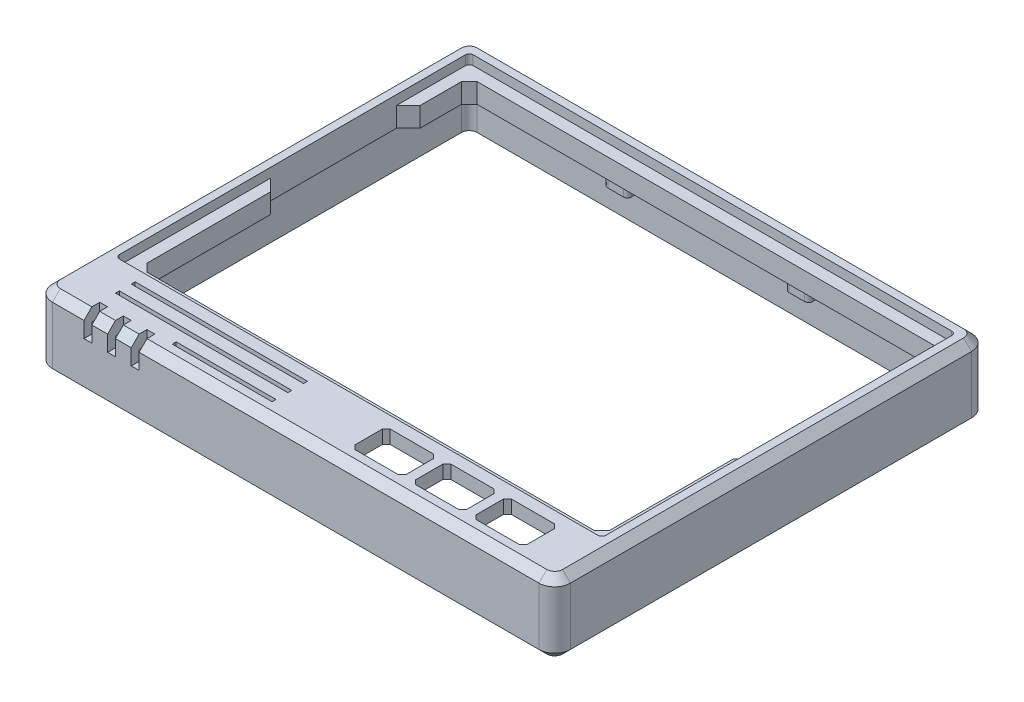
SolidWorks part; units mm, degrees
ref_plane "前视基准面" through (0, 0, 0) normal (0, 0, 1) x (1, 0, 0)
ref_plane "上视基准面" through (0, 0, 0) normal (0, 1, 0) x (1, 0, 0)
ref_plane "右视基准面" through (0, 0, 0) normal (1, 0, 0) x (0, 0, -1)
other "Configuration Table"
sketch "草图1" plane through (0, 0, 0) normal (0, 1, 0) x (1, 0, 0)
  line L1 (-33.1238, 22.1068) -> (32.6362, 22.1068)
  line L2 (-33.1238, 22.1068) -> (-33.1238, -32.8132)
  line L3 (-33.1238, -32.8132) -> (32.6362, -32.8132)
  line L4 (32.6362, 22.1068) -> (32.6362, -32.8132)
  dimension "D1" = 65.76
  dimension "D2" = 54.92
extrude "凸台-拉伸1" add sketch "草图1" against normal blind 9.3
sketch "草图2" plane through (0, 0, 0) normal (0, 1, 0) x (1, 0, 0)
  line L1 (-30.6238, 20.1068) -> (30.1262, 20.1068)
  line L2 (-31.1238, 19.6068) -> (-31.1238, -24.3132)
  line L3 (-30.6238, -24.8132) -> (30.1262, -24.8132)
  line L4 (30.6262, 19.6068) -> (30.6262, -24.3132)
  line L6 (-33.1238, 22.1068) -> (-33.1238, -32.8132) construction
  line L8 (32.6362, 22.1068) -> (-33.1238, 22.1068) construction
  arc A0 (-31.1238, -24.3132) -> (-30.6238, -24.8132) centre (-30.6238, -24.3132) ccw
  arc A1 (30.1262, -24.8132) -> (30.6262, -24.3132) centre (30.1262, -24.3132) ccw
  arc A2 (30.1262, 20.1068) -> (30.6262, 19.6068) centre (30.1262, 19.6068) cw
  arc A3 (-30.6238, 20.1068) -> (-31.1238, 19.6068) centre (-30.6238, 19.6068) ccw
  point P12 (30.6262, -24.8132)
  point P15 (30.6262, 20.1068)
  point P18 (-31.1238, 20.1068)
  dimension "D5" = 0.5
  dimension "D1" = 61.75
  dimension "D2" = 44.92
  dimension "D3" = 2
  dimension "D4" = 2
fillet "圆角1" radius 2 2 edges at (32.6362, -4.65, -22.1068) (-33.1238, -4.65, -22.1068)
extrude "切除-拉伸1" cut sketch "草图2" against normal blind 1.2
sketch "草图3" plane through (0, -1.2, 0) normal (0, 1, 0) x (1, 0, 0)
  line L0 (30.1262, 20.1068) -> (-30.6238, 20.1068) construction
  line L1 (-29.6238, 18.6068) -> (29.1262, 18.6068)
  line L2 (-29.6238, 18.6068) -> (-29.6238, -23.3132)
  line L3 (-29.6238, -23.3132) -> (29.1262, -23.3132)
  line L4 (29.1262, 18.6068) -> (29.1262, -23.3132)
  line L5 (-31.1238, 19.6068) -> (-31.1238, -24.3132) construction
  line L6 (30.6262, -24.3132) -> (30.6262, 19.6068) construction
  line L7 (-30.6238, -24.8132) -> (30.1262, -24.8132) construction
  dimension "D1" = 1.5
  dimension "D2" = 1.5
  dimension "D3" = 1.5
  dimension "D4" = 1.5
extrude "切除-拉伸2" cut sketch "草图3" against normal blind 1
chamfer "倒角2" distance 1 angle 45 5 edges at (32.6362, 0, 6.3532) (32.0504, 0, -21.521) (-0.2438, 0, -22.1068) (-32.5381, 0, -21.521) (-33.1238, 0, 6.3532)
sketch "草图7" plane through (0, -2.2, 0) normal (0, 1, 0) x (1, 0, 0)
  line L0 (-29.6238, -23.3132) -> (29.1262, -23.3132) construction
  line L1 (-29.6238, 18.6068) -> (-27.6238, 18.6068)
  line L2 (-29.6238, 18.6068) -> (-29.6238, -23.3132)
  line L3 (-29.6238, -23.3132) -> (-27.6238, -23.3132)
  line L4 (-27.6238, 18.6068) -> (-27.6238, -23.3132)
  dimension "D1" = 2
extrude "切除-拉伸5" cut sketch "草图7" against normal through all
sketch "草图8" plane through (0, -9.3, 0) normal (0, -1, 0) x (1, 0, 0)
  line L74 (-31.1238, -21.1068) -> (30.6362, -21.1068)
  line L75 (31.6362, -20.1068) -> (31.6362, 31.8132)
  line L76 (31.6362, 31.8132) -> (-32.1238, 31.8132)
  line L77 (-32.1238, 31.8132) -> (-32.1238, -20.1068)
  line L78 (-31.1238, -21.1068) -> (30.6362, -21.1068)
  line L79 (31.6362, -20.1068) -> (31.6362, 31.8132)
  line L80 (31.6362, 31.8132) -> (-32.1238, 31.8132)
  line L81 (-32.1238, 31.8132) -> (-32.1238, -20.1068)
  arc A50 (30.6362, -21.1068) -> (31.6362, -20.1068) centre (30.6362, -20.1068) ccw
  arc A51 (30.6362, -21.1068) -> (31.6362, -20.1068) centre (30.6362, -20.1068) ccw
  arc A52 (-32.1238, -20.1068) -> (-31.1238, -21.1068) centre (-31.1238, -20.1068) ccw
  arc A53 (-32.1238, -20.1068) -> (-31.1238, -21.1068) centre (-31.1238, -20.1068) ccw
  dimension "D1" = 1
extrude "切除-拉伸6" cut sketch "草图8" against normal blind 5.8
sketch "草图10" plane through (0, -1.2, 0) normal (0, 1, 0) x (1, 0, 0)
  line L0 (30.6262, -24.3132) -> (30.6262, 19.6068) construction
  line L1 (29.1262, 18.6068) -> (30.6262, 18.6068)
  line L2 (29.1262, 18.6068) -> (29.1262, -3.6232)
  line L3 (29.1262, -3.6232) -> (30.6262, -3.6232)
  line L4 (30.6262, 18.6068) -> (30.6262, -3.6232)
  dimension "D1" = 22.23
extrude "切除-拉伸7" cut sketch "草图10" against normal blind 1
chamfer "倒角8" distance 3 angle 45 1 edges at (29.1262, -1.7, 3.6232)
chamfer "倒角9" distance 1 angle 45 3 edges at (29.1262, -1.7, 23.3132) (-29.6238, -2.35, 23.3132) (-29.6238, -2.35, -18.6068)
fillet "圆角2" radius 2 2 edges at (32.6362, -5.15, 32.8132) (-33.1238, -5.15, 32.8132)
chamfer "倒角11" distance 1 angle 45 3 edges at (-31.6415, 0, 32.7451) (31.1538, 0, 32.7451) (-0.2438, 0, 32.8132)
fillet "圆角3" radius 1 2 edges at (31.6362, -6.4, 31.8132) (-32.1238, -6.4, 31.8132)
sketch "草图14" plane through (0, 0, 0) normal (0, 1, 0) x (1, 0, 0)
  line L0 (30.6362, -32.8132) -> (-31.1238, -32.8132) construction
  line L1 (-27.1238, -32.8132) -> (-26.1238, -32.8132)
  line L2 (-27.1238, -32.8132) -> (-27.1238, -30.8132)
  line L3 (-27.1238, -30.8132) -> (-26.1238, -30.8132)
  line L4 (-26.1238, -32.8132) -> (-26.1238, -30.8132)
  line L5 (-24.1238, -32.8132) -> (-23.1238, -32.8132)
  line L6 (-24.1238, -32.8132) -> (-24.1238, -30.8132)
  line L7 (-24.1238, -30.8132) -> (-23.1238, -30.8132)
  line L8 (-23.1238, -32.8132) -> (-23.1238, -30.8132)
  line L9 (-32.1238, 20.1068) -> (-32.1238, -30.8132) construction
  line L10 (-21.1238, -32.8132) -> (-20.1238, -32.8132)
  line L11 (-21.1238, -32.8132) -> (-21.1238, -30.8132)
  line L12 (-21.1238, -30.8132) -> (-20.1238, -30.8132)
  line L13 (-20.1238, -32.8132) -> (-20.1238, -30.8132)
  line L14 (-30.6238, -24.8132) -> (30.1262, -24.8132) construction
  line L15 (31.6362, -30.8132) -> (31.6362, 20.1068) construction
  line L16 (-17.9253, -30.3132) -> (-5.2438, -30.3132)
  line L17 (-27.1238, -26.3132) -> (-5.2438, -26.3132)
  line L22 (-27.1238, -26.3132) -> (-27.1238, -26.8132)
  line L23 (-27.1238, -26.8132) -> (-5.2438, -26.8132)
  line L24 (-5.2438, -26.3132) -> (-5.2438, -26.8132)
  line L25 (-27.1238, -28.3132) -> (-5.2438, -28.3132)
  line L26 (-27.1238, -28.3132) -> (-27.1238, -28.8132)
  line L27 (-27.1238, -28.8132) -> (-5.2438, -28.8132)
  line L28 (-5.2438, -28.3132) -> (-5.2438, -28.8132)
  line L29 (-17.9253, -30.3132) -> (-17.9253, -30.8132)
  line L30 (-17.9253, -30.8132) -> (-5.2438, -30.8132)
  line L31 (-5.2438, -30.3132) -> (-5.2438, -30.8132)
  line L32 (4.7562, -26.3132) -> (11.2562, -26.3132)
  line L33 (4.7562, -26.3132) -> (4.7562, -30.8132)
  line L34 (4.7562, -30.8132) -> (11.2562, -30.8132)
  line L35 (11.2562, -26.3132) -> (11.2562, -30.8132)
  line L36 (12.4462, -26.3132) -> (18.9462, -26.3132)
  line L37 (12.4462, -26.3132) -> (12.4462, -30.8132)
  line L38 (12.4462, -30.8132) -> (18.9462, -30.8132)
  line L39 (18.9462, -26.3132) -> (18.9462, -30.8132)
  line L40 (20.1362, -26.3132) -> (26.6362, -26.3132)
  line L41 (20.1362, -26.3132) -> (20.1362, -30.8132)
  line L42 (20.1362, -30.8132) -> (26.6362, -30.8132)
  line L43 (26.6362, -26.3132) -> (26.6362, -30.8132)
  dimension "D1" = 1
  dimension "D2" = 2
  dimension "D3" = 5
  dimension "D4" = 2
  dimension "D5" = 2
  dimension "D6" = 0.5
  dimension "D7" = 1.5
  dimension "D8" = 1.5
  dimension "D9" = 21.88
  dimension "D10" = 1.5
  dimension "D11" = 10
  dimension "D12" = 5
  dimension "D13" = 6.5
  dimension "D14" = 1.19
extrude "切除-拉伸9" cut sketch "草图14" against normal through all contours L17 L24 L23 L22 | L25 L28 L27 L26 | L16 L31 L30 L29 | L32 L35 L34 L33 | L39 L38 L37 L36 | L43 L42 L41 L40
chamfer "倒角14" distance 0.5 angle 45 12 edges at (20.1362, -1.75, 26.3132) (12.4462, -1.75, 26.3132) (4.7562, -1.75, 26.3132) (4.7562, -1.75, 30.8132) (12.4462, -1.75, 30.8132) (20.1362, -1.75, 30.8132) (11.2562, -1.75, 26.3132) (18.9462, -1.75, 26.3132) (11.2562, -1.75, 30.8132) (18.9462, -1.75, 30.8132) (26.6362, -1.75, 26.3132) (26.6362, -1.75, 30.8132)
extrude "切除-拉伸10" cut sketch "草图14<3>" against normal blind 3 contours L4 L3 L2 L1 | L13 L12 L11 L10 | L8 L7 L6 L5
sketch "草图14<3>" plane through (0, 0, 0) normal (0, 1, 0) x (1, 0, 0) same geometry as "草图14"
sketch "草图19" plane through (0, -3.5, 0) normal (0, -1, 0) x (1, 0, 0)
  line L42 (30.6362, 31.8132) -> (-31.1238, 31.8132)
  line L71 (-32.1238, 30.8132) -> (-32.1238, -20.1068)
  line L72 (-31.1238, -21.1068) -> (30.6362, -21.1068)
  line L73 (31.6362, -20.1068) -> (31.6362, 30.8132)
  line L83 (30.6362, 31.8132) -> (-31.1238, 31.8132)
  line L112 (-32.1238, 30.8132) -> (-32.1238, -20.1068)
  line L113 (-31.1238, -21.1068) -> (30.6362, -21.1068)
  line L114 (31.6362, -20.1068) -> (31.6362, 30.8132)
  arc A2 (-31.1238, 31.8132) -> (-32.1238, 30.8132) centre (-31.1238, 30.8132) ccw
  arc A3 (31.6362, 30.8132) -> (30.6362, 31.8132) centre (30.6362, 30.8132) ccw
  arc A4 (-31.1238, 31.8132) -> (-32.1238, 30.8132) centre (-31.1238, 30.8132) ccw
  arc A5 (31.6362, 30.8132) -> (30.6362, 31.8132) centre (30.6362, 30.8132) ccw
  arc A8 (-32.1238, -20.1068) -> (-31.1238, -21.1068) centre (-31.1238, -20.1068) ccw
  arc A9 (-32.1238, -20.1068) -> (-31.1238, -21.1068) centre (-31.1238, -20.1068) ccw
  arc A10 (30.6362, -21.1068) -> (31.6362, -20.1068) centre (30.6362, -20.1068) ccw
  arc A11 (30.6362, -21.1068) -> (31.6362, -20.1068) centre (30.6362, -20.1068) ccw
  dimension "D1" = 0
extrude "切除-拉伸11" cut sketch "草图19" against normal blind 1.8
sketch "草图22" plane through (0, -1.7, 0) normal (0, -1, 0) x (1, 0, 0)
  line L0 (30.6262, 5.1232) -> (30.6262, -18.6068) construction
  line L1 (30.6262, 5.1232) -> (29.1262, 6.6232) construction
  line L2 (29.1262, 22.3132) -> (29.1262, 6.6232) construction
  line L3 (28.1262, 23.3132) -> (29.1262, 22.3132) construction
  line L4 (30.6262, 5.1232) -> (30.6262, -18.6068)
  line L5 (30.6262, 5.1232) -> (29.1262, 6.6232)
  line L6 (29.1262, 22.3132) -> (29.1262, 6.6232)
  line L7 (28.1262, 23.3132) -> (29.1262, 22.3132)
  line L8 (28.1262, 23.3132) -> (28.1262, 31.8132)
  line L10 (28.1262, 31.8132) -> (30.6362, 31.8132)
  line L12 (31.6362, -20.1068) -> (31.6362, 30.8132) construction
  line L13 (31.6362, -20.1068) -> (31.6362, 30.8132)
  line L14 (-28.6238, 23.3132) -> (-28.6238, 31.8132)
  line L15 (30.6362, 31.8132) -> (-31.1238, 31.8132) construction
  line L16 (-28.6238, 31.8132) -> (-31.1238, 31.8132)
  line L19 (-29.6238, 22.3132) -> (-28.6238, 23.3132) construction
  line L20 (-29.6238, -17.6068) -> (-29.6238, 22.3132) construction
  line L21 (-28.6238, -18.6068) -> (-29.6238, -17.6068) construction
  line L22 (-29.6238, 22.3132) -> (-28.6238, 23.3132)
  line L23 (-29.6238, -17.6068) -> (-29.6238, 22.3132)
  line L24 (-28.6238, -18.6068) -> (-29.6238, -17.6068)
  line L26 (-32.1238, 30.8132) -> (-32.1238, -20.1068) construction
  line L27 (-32.1238, 30.8132) -> (-32.1238, -20.1068)
  line L28 (-31.1238, -21.1068) -> (30.6362, -21.1068) construction
  line L29 (30.6262, -18.6068) -> (-28.6238, -18.6068) construction
  line L30 (-31.1238, -21.1068) -> (30.6362, -21.1068)
  line L31 (30.6262, -18.6068) -> (-28.6238, -18.6068)
  arc A0 (31.6362, 30.8132) -> (30.6362, 31.8132) centre (30.6362, 30.8132) ccw construction
  arc A1 (30.6362, -21.1068) -> (31.6362, -20.1068) centre (30.6362, -20.1068) ccw construction
  arc A2 (31.6362, 30.8132) -> (30.6362, 31.8132) centre (30.6362, 30.8132) ccw
  arc A3 (30.6362, -21.1068) -> (31.6362, -20.1068) centre (30.6362, -20.1068) ccw
  arc A4 (-31.1238, 31.8132) -> (-32.1238, 30.8132) centre (-31.1238, 30.8132) ccw construction
  arc A5 (-32.1238, -20.1068) -> (-31.1238, -21.1068) centre (-31.1238, -20.1068) ccw construction
  arc A6 (-31.1238, 31.8132) -> (-32.1238, 30.8132) centre (-31.1238, 30.8132) ccw
  arc A7 (-32.1238, -20.1068) -> (-31.1238, -21.1068) centre (-31.1238, -20.1068) ccw
  point P7 (28.1262, 31.8132)
extrude "凸台-拉伸3" add sketch "草图22" along normal blind 2
fillet "圆角5" radius 1 2 edges at (28.1262, -1.7, 27.5632) (-28.6238, -1.7, 27.5632)
sketch "草图23" plane through (0, -3.7, 0) normal (0, -1, 0) x (1, 0, 0)
  line L0 (-28.6238, 23.3132) -> (-28.6238, 31.8132) construction
  line L1 (-31.1238, -21.1068) -> (30.6362, -21.1068) construction
  line L2 (30.6362, 31.8132) -> (-31.1238, 31.8132) construction
  line L3 (-13.2438, -19.3068) -> (-10.2438, -19.3068)
  line L4 (28.1262, 31.8132) -> (28.1262, 23.3132) construction
  line L5 (-31.1238, -21.1068) -> (30.6362, -21.1068) construction
  line L6 (-13.2438, -19.3068) -> (-13.2438, -21.1068)
  line L15 (-32.1238, 30.8132) -> (-32.1238, -20.1068) construction
  line L16 (-28.6238, 23.3132) -> (-32.1238, 23.3132)
  line L17 (-28.6238, 23.3132) -> (-28.6238, 24.8132)
  line L18 (-28.6238, 24.8132) -> (-32.1238, 24.8132)
  line L19 (-32.1238, 23.3132) -> (-32.1238, 24.8132)
  line L20 (31.6362, -20.1068) -> (31.6362, 30.8132) construction
  line L21 (28.1262, 23.3132) -> (31.6362, 23.3132)
  line L22 (28.1262, 23.3132) -> (28.1262, 24.8132)
  line L23 (28.1262, 24.8132) -> (31.6362, 24.8132)
  line L24 (31.6362, 23.3132) -> (31.6362, 24.8132)
  line L25 (-13.2438, -21.1068) -> (-10.2438, -21.1068)
  line L26 (-10.2438, -19.3068) -> (-10.2438, -21.1068)
  line L28 (9.7562, -19.3068) -> (12.7562, -19.3068)
  line L29 (9.7562, -19.3068) -> (9.7562, -21.1068)
  line L30 (9.7562, -21.1068) -> (12.7562, -21.1068)
  line L31 (12.7562, -19.3068) -> (12.7562, -21.1068)
  circle A0 centre (-30.4238, 30.0132) radius 1
  circle A1 centre (-30.4238, -19.3068) radius 1
  circle A2 centre (29.9262, 30.0132) radius 1
  point P38 (-0.2438, -21.1068)
  dimension "D1" = 1.8
  dimension "D3" = 2
  dimension "D2" = 1.8
  dimension "D4" = 1.8
  dimension "D5" = 1.8
  dimension "D6" = 1.5
  dimension "D7" = 1.5
  dimension "D8" = 3
  dimension "D9" = 10
  dimension "D10" = 10
extrude "切除-拉伸14" cut sketch "草图23" against normal blind 2 contours A1 | A2 | A0
extrude "凸台-拉伸4" add sketch "草图23<3>" along normal blind 1.6 contours L23 L24 L21 L22 | L18 L19 L16 L17 | L3 L26 L25 L6 | L28 L31 L30 L29
sketch "草图23<3>" plane through (0, -3.7, 0) normal (0, -1, 0) x (1, 0, 0) same geometry as "草图23"
fillet "圆角7" radius 0.5 6 edges at (12.7562, -4.5, -19.3068) (-10.2438, -4.5, -19.3068) (9.7562, -4.5, -19.3068) (-13.2438, -4.5, -19.3068) (28.1262, -4.5, 24.8132) (-28.6238, -4.5, 24.8132)
sketch "草图26" plane through (0, -1.7, 0) normal (0, -1, 0) x (1, 0, 0)
  line L1 (1.2562, 31.8132) -> (-1.7438, 31.8132)
  line L2 (1.2562, 31.8132) -> (1.2562, 30.3132)
  line L3 (1.2562, 30.3132) -> (-1.7438, 30.3132)
  line L4 (-1.7438, 31.8132) -> (-1.7438, 30.3132)
  line L5 (30.6362, 31.8132) -> (-31.1238, 31.8132) construction
  point P8 (-0.2438, 31.8132)
  point P9 (-0.2438, 31.8132)
  dimension "D1" = 1.5
  dimension "D2" = 3
extrude "凸台-拉伸6" add sketch "草图26" along normal blind 2
chamfer "倒角18" distance 1.5 angle 45 2 edges at (1.2562, -2.7, 31.8132) (-1.7438, -2.7, 31.8132)
sketch "草图28" plane through (0, -1.2, 0) normal (0, 1, 0) x (1, 0, 0)
  line L0 (30.6262, -5.1232) -> (-31.1238, -5.1232) construction
  line L1 (-31.1238, 19.6068) -> (-31.1238, -24.3132) construction
  line L2 (29.1262, -6.6232) -> (-29.6238, -6.6232) construction
  line L3 (-29.6238, 17.6068) -> (-29.6238, -22.3132) construction
  line L4 (-31.1238, -5.1232) -> (-29.6238, -6.6232)
  line L5 (-29.6238, 17.6068) -> (-29.6238, 12.3768) construction
  line L6 (-29.6238, 12.3768) -> (-31.1238, 10.8768)
  line L7 (-29.6238, 17.6068) -> (-28.6238, 18.6068) construction
  line L8 (-31.1238, 10.8768) -> (-31.1238, -5.1232)
  line L9 (-29.6238, -6.6232) -> (-29.6238, 12.3768)
  line L10 (-29.6238, 17.6068) -> (-31.1238, 17.6068) construction
  dimension "D1" = 6.73
extrude "切除-拉伸15" cut sketch "草图28" against normal through all
chamfer "倒角19" distance 1 angle 45 8 edges at (-0.2438, -9.3, 32.8132) (32.0504, -9.3, 32.2275) (-32.5381, -9.3, 32.2275) (32.6362, -9.3, 5.3532) (-33.1238, -9.3, 5.3532) (32.0504, -9.3, -21.521) (-32.5381, -9.3, -21.521) (-0.2438, -9.3, -22.1068)
